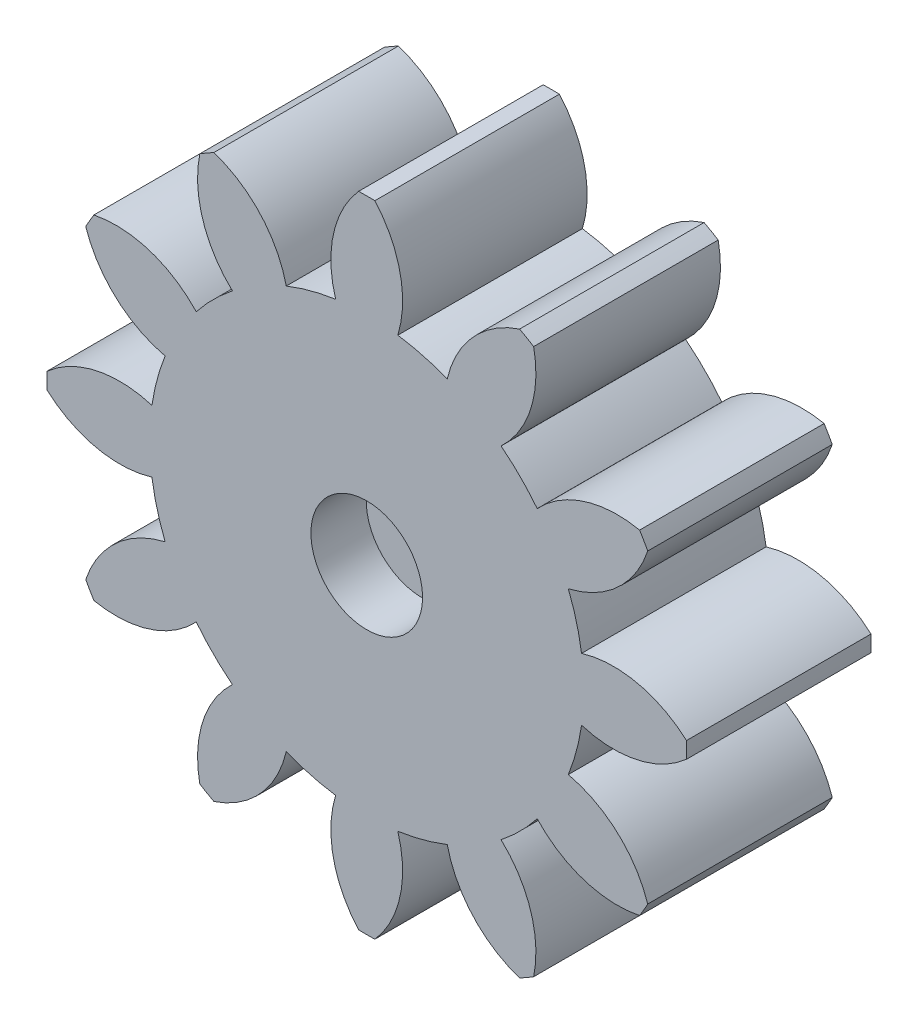
SolidWorks part; units mm, degrees
ref_plane "Front Plane" through (0, 0, 0) normal (0, 0, 1) x (1, 0, 0)
ref_plane "Top Plane" through (0, 0, 0) normal (0, 1, 0) x (1, 0, 0)
ref_plane "Right Plane" through (0, 0, 0) normal (1, 0, 0) x (0, 0, -1)
sketch "Sketch1" plane through (0, 0, 0) normal (0, 0, 1) x (1, 0, 0)
  arc A96 (10.9244, -4.3614) -> (11.6416, -1.6851) centre (0, 0) ccw
  arc A97 (11.6416, -1.6851) -> (17.3299, -0.4402) centre (13.3779, 3.9992) ccw
  arc A98 (17.3299, -0.4402) -> (17.3299, 0.4402) centre (0, 0) ccw
  arc A99 (17.3299, 0.4402) -> (11.6416, 1.6851) centre (13.3779, -3.9992) ccw
  arc A100 (11.6416, 1.6851) -> (10.9244, 4.3614) centre (0, 0) ccw
  arc A101 (10.9244, 4.3614) -> (15.2282, 8.2838) centre (9.586, 10.1524) ccw
  arc A102 (15.2282, 8.2838) -> (14.7881, 9.0462) centre (0, 0) ccw
  arc A103 (14.7881, 9.0462) -> (9.2393, 7.2801) centre (13.5852, 3.2255) ccw
  arc A104 (9.2393, 7.2801) -> (7.2801, 9.2393) centre (0, 0) ccw
  arc A105 (7.2801, 9.2393) -> (9.0462, 14.7881) centre (3.2255, 13.5852) ccw
  arc A106 (9.0462, 14.7881) -> (8.2838, 15.2282) centre (0, 0) ccw
  arc A107 (8.2838, 15.2282) -> (4.3614, 10.9244) centre (10.1524, 9.586) ccw
  arc A108 (4.3614, 10.9244) -> (1.6851, 11.6416) centre (0, 0) ccw
  arc A109 (1.6851, 11.6416) -> (0.4402, 17.3299) centre (-3.9992, 13.3779) ccw
  arc A110 (0.4402, 17.3299) -> (-0.4402, 17.3299) centre (0, 0) ccw
  arc A111 (-0.4402, 17.3299) -> (-1.6851, 11.6416) centre (3.9992, 13.3779) ccw
  arc A112 (-1.6851, 11.6416) -> (-4.3614, 10.9244) centre (0, 0) ccw
  arc A113 (-4.3614, 10.9244) -> (-8.2838, 15.2282) centre (-10.1524, 9.586) ccw
  arc A114 (-8.2838, 15.2282) -> (-9.0462, 14.7881) centre (0, 0) ccw
  arc A115 (-9.0462, 14.7881) -> (-7.2801, 9.2393) centre (-3.2255, 13.5852) ccw
  arc A116 (-7.2801, 9.2393) -> (-9.2393, 7.2801) centre (0, 0) ccw
  arc A117 (-9.2393, 7.2801) -> (-14.7881, 9.0462) centre (-13.5852, 3.2255) ccw
  arc A118 (-14.7881, 9.0462) -> (-15.2282, 8.2838) centre (0, 0) ccw
  arc A119 (-15.2282, 8.2838) -> (-10.9244, 4.3614) centre (-9.586, 10.1524) ccw
  arc A120 (-10.9244, 4.3614) -> (-11.6416, 1.6851) centre (0, 0) ccw
  arc A121 (-11.6416, 1.6851) -> (-17.3299, 0.4402) centre (-13.3779, -3.9992) ccw
  arc A122 (-17.3299, 0.4402) -> (-17.3299, -0.4402) centre (0, 0) ccw
  arc A123 (-17.3299, -0.4402) -> (-11.6416, -1.6851) centre (-13.3779, 3.9992) ccw
  arc A124 (-11.6416, -1.6851) -> (-10.9244, -4.3614) centre (0, 0) ccw
  arc A125 (-10.9244, -4.3614) -> (-15.2282, -8.2838) centre (-9.586, -10.1524) ccw
  arc A126 (-15.2282, -8.2838) -> (-14.7881, -9.0462) centre (0, 0) ccw
  arc A127 (-14.7881, -9.0462) -> (-9.2393, -7.2801) centre (-13.5852, -3.2255) ccw
  arc A128 (-9.2393, -7.2801) -> (-7.2801, -9.2393) centre (0, 0) ccw
  arc A129 (-7.2801, -9.2393) -> (-9.0462, -14.7881) centre (-3.2255, -13.5852) ccw
  arc A130 (-9.0462, -14.7881) -> (-8.2838, -15.2282) centre (0, 0) ccw
  arc A131 (-8.2838, -15.2282) -> (-4.3614, -10.9244) centre (-10.1524, -9.586) ccw
  arc A132 (-4.3614, -10.9244) -> (-1.6851, -11.6416) centre (0, 0) ccw
  arc A133 (-1.6851, -11.6416) -> (-0.4402, -17.3299) centre (3.9992, -13.3779) ccw
  arc A134 (-0.4402, -17.3299) -> (0.4402, -17.3299) centre (0, 0) ccw
  arc A135 (0.4402, -17.3299) -> (1.6851, -11.6416) centre (-3.9992, -13.3779) ccw
  arc A136 (1.6851, -11.6416) -> (4.3614, -10.9244) centre (0, 0) ccw
  arc A137 (4.3614, -10.9244) -> (8.2838, -15.2282) centre (10.1524, -9.586) ccw
  arc A138 (8.2838, -15.2282) -> (9.0462, -14.7881) centre (0, 0) ccw
  arc A139 (9.0462, -14.7881) -> (7.2801, -9.2393) centre (3.2255, -13.5852) ccw
  arc A140 (7.2801, -9.2393) -> (9.2393, -7.2801) centre (0, 0) ccw
  arc A141 (9.2393, -7.2801) -> (14.7881, -9.0462) centre (13.5852, -3.2255) ccw
  arc A142 (14.7881, -9.0462) -> (15.2282, -8.2838) centre (0, 0) ccw
  arc A143 (15.2282, -8.2838) -> (10.9244, -4.3614) centre (9.586, -10.1524) ccw
extrude "Boss-Extrude1" add sketch "Sketch1" along normal blind 10
sketch "Sketch3" plane through (0, 0, 10) normal (0, 0, 1) x (1, 0, 0)
  circle A0 centre (0, 0) radius 3.025
  dimension "D1" = 6.05
extrude "Cut-Extrude1" cut sketch "Sketch3" against normal blind 3
sketch "Sketch4" plane through (0, 0, 0) normal (0, 0, -1) x (-1, 0, 0)
  circle A0 centre (0, 0) radius 3.025 construction
  circle A1 centre (0, 0) radius 3.025
extrude "Cut-Extrude2" cut sketch "Sketch4" against normal offset from surface (5 mm away) 2 up to face at (3.025, 0, 7)
sketch "Sketch5" plane through (0, 0, 5) normal (0, 0, -1) x (-1, 0, 0)
  circle A0 centre (0, 0) radius 1.125
  dimension "D1" = 2.25
extrude "Cut-Extrude3" cut sketch "Sketch5" against normal up to next
sketch "Sketch6" plane through (0, 0, 0) normal (0, 0, -1) x (-1, 0, 0)
  text T0 "<i>Top</i>" font "Century Gothic" height in points 8
extrude "Cut-Extrude4" cut sketch "Sketch6" against normal blind 0.4
sketch "Sketch7" plane through (0, 0, 10) normal (0, 0, 1) x (1, 0, 0)
  point P0 (0, 0)
sketch "Sketch8" plane through (0, 0, 10) normal (0, 0, 1) x (1, 0, 0)
  line L0 (0, 0) -> (0, -17.3355) construction
  arc A0 (-0.4402, -17.3299) -> (0.4402, -17.3299) centre (0, 0) ccw construction
